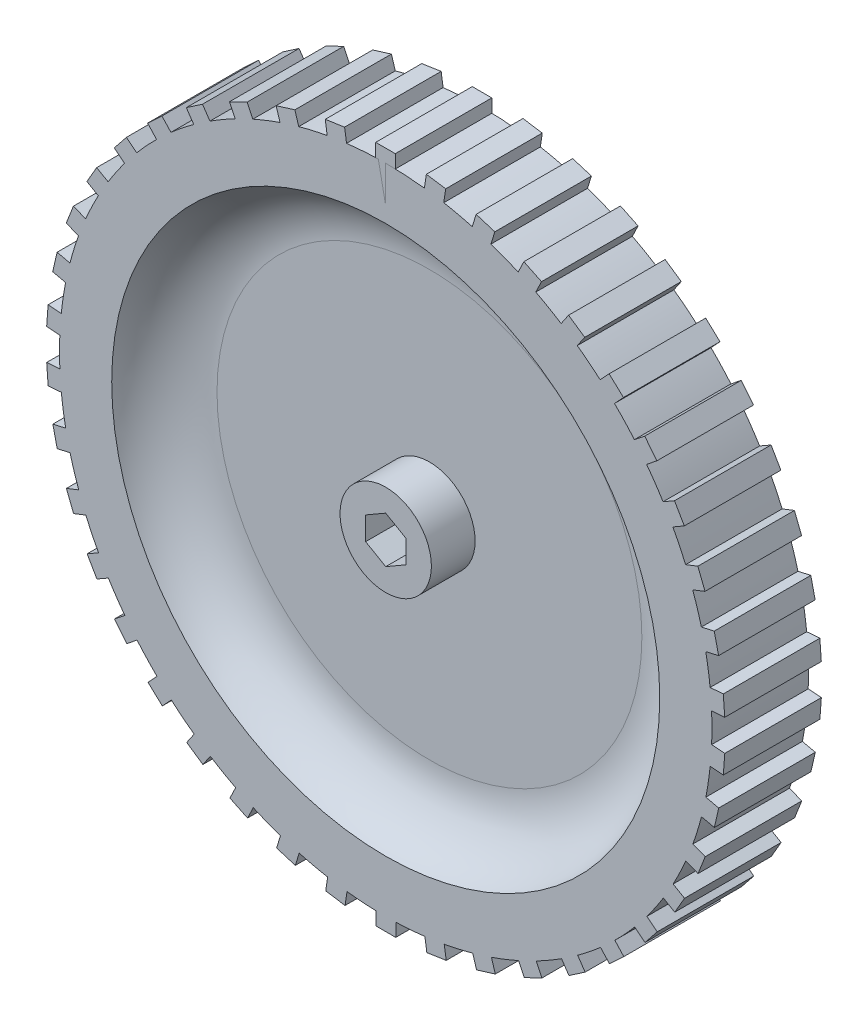
SolidWorks part; units mm, degrees
ref_plane "Front Plane" through (0, 0, 0) normal (0, 0, 1) x (1, 0, 0)
ref_plane "Top Plane" through (0, 0, 0) normal (0, 1, 0) x (1, 0, 0)
ref_plane "Right Plane" through (0, 0, 0) normal (1, 0, 0) x (0, 0, -1)
sketch "Sketch1" plane through (0, 0, 0) normal (0, 0, 1) x (1, 0, 0)
  circle A0 centre (0, 0) radius 50
  dimension "D1" = 100
extrude "Boss-Extrude1" add sketch "Sketch1" along normal blind 14.8
sketch "Sketch2" plane through (0, 0, 14.8) normal (0, 0, 1) x (1, 0, 0)
  line L1 (0, -3.5507) -> (3.075, -1.7754)
  line L2 (3.075, -1.7754) -> (3.075, 1.7754)
  line L3 (3.075, 1.7754) -> (0, 3.5507)
  line L4 (0, 3.5507) -> (-3.075, 1.7754)
  line L5 (-3.075, 1.7754) -> (-3.075, -1.7754)
  line L6 (-3.075, -1.7754) -> (0, -3.5507)
  circle A0 centre (0, 0) radius 3.075 construction
  dimension "D1" = 6.15
extrude "Cut-Extrude1" cut sketch "Sketch2" against normal up to next
sketch "Sketch3" plane through (0, 0, 0) normal (0, 0, -1) x (-1, 0, 0)
  circle A0 centre (0, 0) radius 3.5507
extrude "Cut-Extrude3" cut sketch "Sketch3" against normal blind 5.5
sketch "Sketch4" plane through (0, 0, 14.8) normal (0, 0, 1) x (1, 0, 0)
  circle A0 centre (0, 22.5) radius 10
  dimension "D1" = 20
  dimension "D2" = 22.5
extrude "Cut-Extrude4" [suppressed] cut sketch "Sketch4" against normal up to next
sketch "Sketch6" plane through (0, 0, 0) normal (1, 0, 0) x (0, 0, -1)
  line L0 (-14.8, 0) -> (2.0132, 0) construction
  line L1 (-14.8, 50) -> (-14.8, -50) construction
pattern_circular "CirPattern4" [suppressed] count 5 over 360 of bodies 105
sketch "Sketch9" plane through (0, 0, 0) normal (0, 1, 0) x (1, 0, 0)
  line L0 (-3.075, -14.8) -> (0, -14.8) construction
  line L1 (-1.5375, -14.8) -> (1.4625, -14.8)
  line L2 (-1.5375, -14.8) -> (-1.5375, 0)
  line L3 (-1.5375, 0) -> (1.4625, 0)
  line L4 (1.4625, -14.8) -> (1.4625, 0)
  line L5 (50, 0) -> (-50, 0) construction
  dimension "D1" = 3
extrude "Boss-Extrude3" add sketch "Sketch9" along normal blind 12 from offset 40 separate body
pattern_circular "CirPattern11" count 42 over 360 about axis through (0, 0, 14.8) along (0, 0, -1) of "Boss-Extrude3"
sketch "Sketch10" plane through (0, 0, 0) normal (0, 0, -1) x (-1, 0, 0)
  circle A0 centre (0, 0) radius 4.7507
  circle A1 centre (0, 0) radius 3.5507 construction
  dimension "D1" = 1.2
extrude "Boss-Extrude4" [suppressed] add sketch "Sketch10" along normal blind 1.6
sketch "Sketch11" [suppressed] plane through (0, 0, -1.6) normal (0, 0, -1) x (-1, 0, 0)
  circle A0 centre (0, 0) radius 3.55
  dimension "D1" = 7.1
extrude "Cut-Extrude5" [suppressed] cut sketch "Sketch11" against normal up to next
sketch "Sketch12" plane through (0, 0, 14.8) normal (0, 0, 1) x (1, 0, 0)
  circle A0 centre (0, 0) radius 42
  circle A1 centre (0, 0) radius 7
  arc A2 (-49.0655, 9.6218) -> (-49.7296, 5.1933) centre (0, 0) ccw construction
  dimension "D1" = 14
  dimension "D2" = 8
extrude "Cut-Extrude6" cut sketch "Sketch12" against normal blind 6.7
fillet "Fillet1" radius 10 1 edges at (-0.0375, 42, 8.1)
